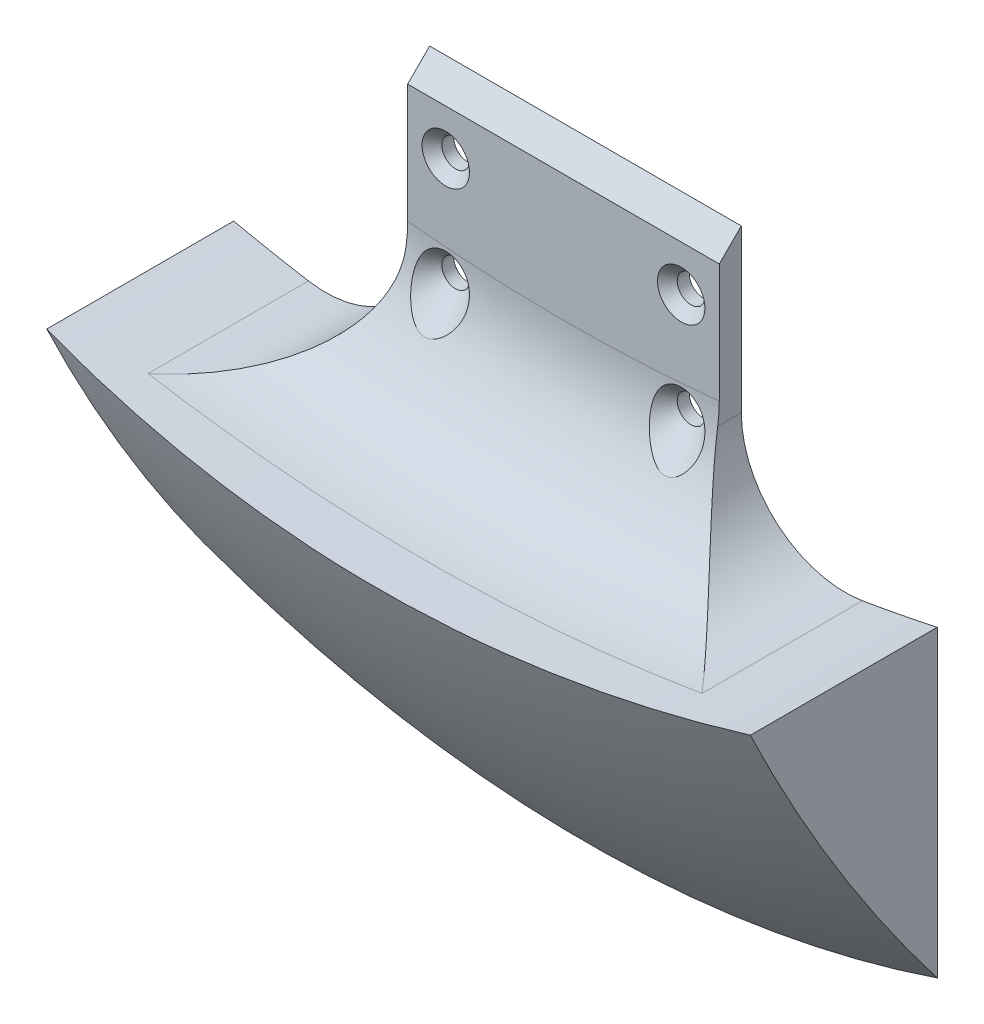
SolidWorks part; units mm, degrees
ref_plane "Front Plane" through (0, 0, 0) normal (0, 0, 1) x (1, 0, 0)
ref_plane "Top Plane" through (0, 0, 0) normal (0, 1, 0) x (1, 0, 0)
ref_plane "Right Plane" through (0, 0, 0) normal (1, 0, 0) x (0, 0, -1)
sketch "Sketch1" plane through (0, 0, 0) normal (0, 0, 1) x (1, 0, 0)
  line L0 (22.5, -24.1344) -> (22.5, -17.5044) construction
  line L1 (22.5, -63.5) -> (-22.5, -63.5)
  line L2 (22.5, -63.5) -> (22.5, 0)
  line L3 (22.5, 0) -> (-22.5, 0)
  line L4 (-22.5, -63.5) -> (-22.5, 0)
  line L5 (22.5, -63.5) -> (-22.5, 0) construction
  line L6 (22.5, 0) -> (-22.5, -63.5) construction
  line L7 (-22.5, -24.1344) -> (-22.5, -17.5044) construction
  line L9 (50.8, -76.6885) -> (50.8, -39.4374) construction
  line L11 (50.8, -85.1568) -> (50.8, -36.0454)
  line L13 (-50.8, -36.0454) -> (-50.8, -73.6149) construction
  line L15 (-50.8, -36.0454) -> (-50.8, -85.1568)
  arc A0 (-64.5496, -79.9608) -> (-40.722, -88.1001) centre (0, 70.0602) ccw
  arc A2 (-50.8, -85.1568) -> (50.8, -85.1568) centre (0, 70.0602) ccw
  arc A3 (40.722, -88.1001) -> (64.5496, -79.9608) centre (0, 70.0602) ccw
  arc A4 (6, -93.1482) -> (29.7253, -90.5305) centre (0, 70.0602) ccw
  arc A5 (-29.7253, -90.5305) -> (-6, -93.1482) centre (0, 70.0602) ccw
  arc A7 (-29.7253, -90.5305) -> (-6, -93.1482) centre (0, 70.0602) ccw
  arc A8 (6, -93.1482) -> (29.7253, -90.5305) centre (0, 70.0602) ccw
  arc A9 (40.722, -88.1001) -> (64.5496, -79.9608) centre (0, 70.0602) ccw
  ellipse E0 centre (0, 139.4577) end of major axis (208.9237, 139.4577) minor radius 180.9332 (-50.8, -36.0454) -> (50.8, -36.0454) ccw construction
  ellipse E2 centre (0, 139.4577) end of major axis (208.9237, 139.4577) minor radius 180.9332 (-50.8, -36.0454) -> (50.8, -36.0454) ccw
  point P0 (0, -31.75)
  point P23 (0, -63.5)
  dimension "D1" = 63.5
extrude "Boss-Extrude1" add sketch "Sketch1" along normal blind 3.175 contours L2 L3 L4 L1
sketch "Sketch2" plane through (0, 0, 0) normal (0, 0, -1) x (-1, 0, 0)
  line L22 (-50.8, -36.0454) -> (-50.8, -85.1568)
  line L23 (50.8, -85.1568) -> (50.8, -36.0454)
  line L32 (-50.8, -36.0454) -> (-50.8, -85.1568)
  line L33 (50.8, -85.1568) -> (50.8, -36.0454)
  arc A4 (-50.8, -85.1568) -> (50.8, -85.1568) centre (0, 70.0602) ccw
  arc A5 (-50.8, -85.1568) -> (50.8, -85.1568) centre (0, 70.0602) ccw
  ellipse E2 centre (0, 139.4577) end of major axis (-208.9237, 139.4577) minor radius 180.9332 (-50.8, -36.0454) -> (50.8, -36.0454) ccw
  ellipse E3 centre (0, 139.4577) end of major axis (-208.9237, 139.4577) minor radius 180.9332 (-50.8, -36.0454) -> (50.8, -36.0454) ccw
  dimension "D2" = 0
extrude "Boss-Extrude3" add sketch "Sketch2" against normal up to surface (26.994 mm away)
fillet "Fillet2" radius 20 1 edges at (0, -41.4755, 3.175)
sketch "Sketch3" plane through (0, 0, 0) normal (0, 0, -1) x (-1, 0, 0)
  circle A0 centre (17, -24.75) radius 2
  circle A1 centre (-17, -24.75) radius 2
  circle A2 centre (-17, -9.75) radius 2
  circle A3 centre (17, -9.75) radius 2
  dimension "D1" = 4
extrude "Cut-Extrude1" cut sketch "Sketch3" against normal through all
ref_plane "Plane1" through (0, 0, 1.75) normal (0, 0, -1) x (-1, 0, 0)
sketch "Sketch5" plane through (0, 0, 1.75) normal (0, 0, -1) x (-1, 0, 0)
  circle A0 centre (17, -9.75) radius 2 construction
  circle A1 centre (17, -24.75) radius 2 construction
  circle A2 centre (-17, -9.75) radius 2 construction
  circle A3 centre (-17, -24.75) radius 2 construction
  circle A4 centre (17, -9.75) radius 2
  circle A5 centre (17, -24.75) radius 2
  circle A6 centre (-17, -9.75) radius 2
  circle A7 centre (-17, -24.75) radius 2
extrude "Cut-Extrude2" cut sketch "Sketch5" against normal blind 10 draft 45 draft outward yes
fillet "Fillet3" radius 15 2 edges at (22.5, -40.4232, 11.5875) (-22.5, -40.4232, 11.5875)
chamfer "Chamfer3" distance 3.175 angle 45 1 edges at (0, 0, 3.175)
